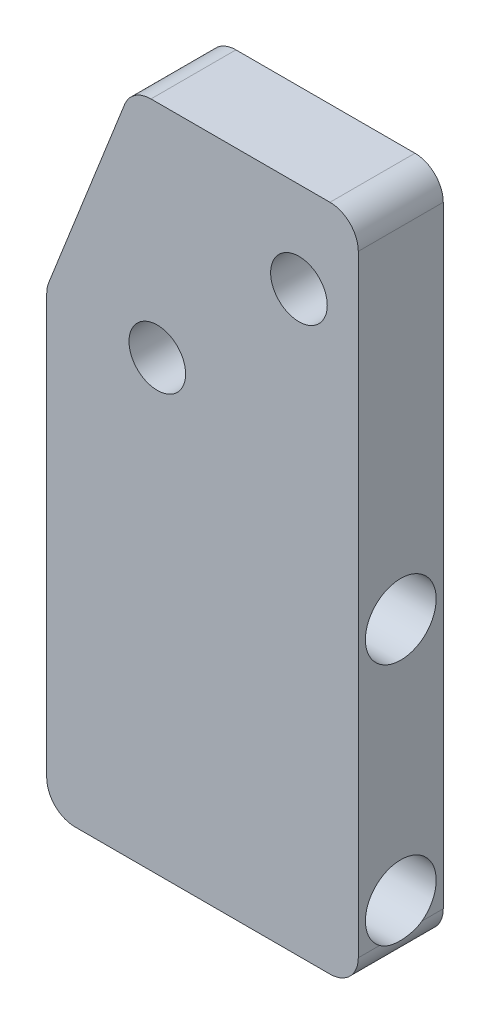
SolidWorks part; units mm, degrees
ref_plane "Front Plane" through (0, 0, 0) normal (0, 0, 1) x (1, 0, 0)
ref_plane "Top Plane" through (0, 0, 0) normal (0, 1, 0) x (1, 0, 0)
ref_plane "Right Plane" through (0, 0, 0) normal (1, 0, 0) x (0, 0, -1)
sketch "Sketch1" plane through (0, 0, 0) normal (0, 0, 1) x (1, 0, 0)
  line L0 (0, 0) -> (0, -149.86)
  line L1 (0, -149.86) -> (-69.85, -149.86)
  line L2 (-69.85, -149.86) -> (-69.85, -48.26)
  line L3 (-69.85, -48.26) -> (-50.8, 0)
  line L4 (-50.8, 0) -> (0, 0)
  dimension "D1" = 149.86
  dimension "D2" = 69.85
  dimension "D3" = 101.6
  dimension "D4" = 50.8
extrude "Boss-Extrude1" add sketch "Sketch1" along normal blind 19.05
sketch "Sketch2" plane through (0, 0, 0) normal (1, 0, 0) x (0, 0, -1)
  line L0 (0, -149.86) -> (0, 0) construction
  line L1 (-19.05, -149.86) -> (0, -149.86) construction
  line L2 (-19.05, 0) -> (0, 0) construction
  circle A0 centre (-9.525, -82.55) radius 7.9375
  circle A1 centre (-9.525, -137.16) radius 7.9375
  dimension "D1" = 15.875
  dimension "D2" = 15.875
  dimension "D3" = 9.525
  dimension "D4" = 9.525
  dimension "D5" = 12.7
  dimension "D6" = 82.55
extrude "Cut-Extrude1" cut sketch "Sketch2" against normal blind 15.24
sketch "Sketch3" plane through (0, 0, 19.05) normal (0, 0, 1) x (1, 0, 0)
  line L0 (0, -149.86) -> (0, 0) construction
  line L1 (-69.85, -149.86) -> (0, -149.86) construction
  circle A0 centre (-45.0596, -49.53) radius 6.35
  circle A1 centre (-13.3096, -20.32) radius 6.35
  point P4 (-108.5596, -109.855)
  point P7 (21.4687, -109.855)
  dimension "D4" = 12.7
  dimension "D5" = 12.7
  dimension "D1" = 108.5596
  dimension "D2" = 60.325
  dimension "D3" = 89.535
  dimension "D6" = 63.5
  dimension "D8" = 40.005
  dimension "D10" = 95.25
extrude "Cut-Extrude3" cut sketch "Sketch3" against normal through all
fillet "Fillet1" radius 6.35 5 edges at (-50.8, 0, 9.525) (0, 0, 9.525) (0, -149.86, 9.525) (-69.85, -149.86, 9.525) (-69.85, -48.26, 9.525)
